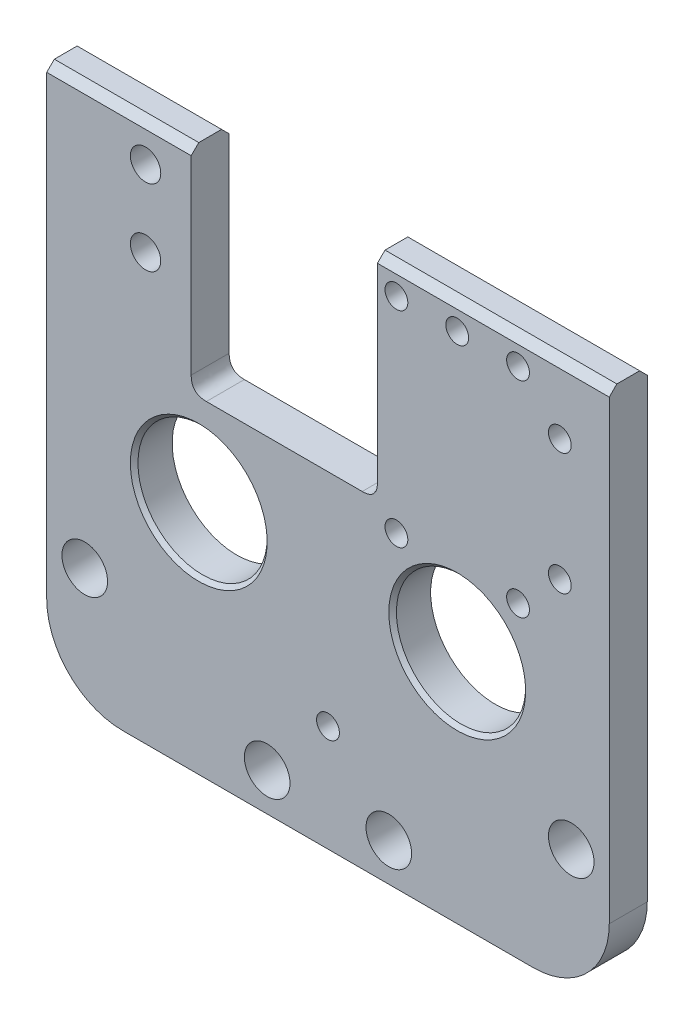
SolidWorks part; units mm, degrees
material "Stop 1060"
ref_plane "Płaszczyzna przednia" through (0, 0, 0) normal (0, 0, 1) x (1, 0, 0)
ref_plane "Płaszczyzna górna" through (0, 0, 0) normal (0, 1, 0) x (1, 0, 0)
ref_plane "Płaszczyzna prawa" through (0, 0, 0) normal (1, 0, 0) x (0, 0, -1)
sketch "Szkic1" plane through (0, 0, 0) normal (0, 0, 1) x (1, 0, 0)
  line L2 (34, 36) -> (34, -35)
  line L3 (34, -35) -> (-20, -35)
  line L6 (-20, -35) -> (-20, 36)
  line L7 (-20, 36) -> (34, 36)
  dimension "D1" = 71
  dimension "D2" = 20
  dimension "D3" = 54
  dimension "D4" = 36
extrude "Dodanie-wyciągnięcie1" add sketch "Szkic1" along normal blind 5
sketch "Szkic2" plane through (0, 0, 5) normal (0, 0, 1) x (1, 0, 0)
  line L1 (-20, 36) -> (3.5, 36)
  line L2 (-20, 36) -> (-20, 8)
  line L3 (-20, 8) -> (3.5, 8)
  line L4 (3.5, 36) -> (3.5, 8)
  dimension "D1" = 28
  dimension "D2" = 23.5
extrude "Wytnij-wyciągnięcie1" cut sketch "Szkic2" against normal blind 5
sketch "Szkic3" plane through (0, 0, 0) normal (0, 0, -1) x (-1, 0, 0)
  line L0 (-3.5, 8) -> (-3.5, 36) construction
  line L1 (-3.5, 30.5) -> (-24.5, 30.5)
  line L2 (-3.5, 30.5) -> (-3.5, 9.5)
  line L3 (-3.5, 9.5) -> (-24.5, 9.5)
  line L4 (-24.5, 30.5) -> (-24.5, 9.5)
  line L5 (-34, 36) -> (-3.5, 36) construction
  dimension "D1" = 5.5
  dimension "D2" = 21
  dimension "D3" = 21
extrude "Wytnij-wyciągnięcie2" cut sketch "Szkic3" against normal blind 3
sketch "Szkic4" plane through (0, 0, 5) normal (0, 0, 1) x (1, 0, 0)
  line L0 (3.5, 8) -> (3.5, 36) construction
  line L1 (34, 36) -> (3.5, 36) construction
  circle A0 centre (6, 32.5) radius 1.5
  circle A1 centre (14, 32.5) radius 1.5
  circle A2 centre (22, 32.5) radius 1.5
  circle A4 centre (22, 5.5) radius 1.5
  circle A5 centre (6, 5.5) radius 1.5
  circle A6 centre (27.5, 27) radius 1.5
  circle A7 centre (27.5, 11) radius 1.5
  circle A8 centre (14, 5.5) radius 1.5 [skipped]
  dimension "D1" = 2.5
  dimension "D2" = 3
  dimension "D4" = 3
  dimension "D6" = 8
  dimension "D8" = 5.5
  dimension "D10" = 3
  dimension "D3" = 3.5
  dimension "D5" = 2
  dimension "D7" = 27
  dimension "D9" = 5.5
  dimension "D11" = 2
extrude "Wytnij-wyciągnięcie3" cut sketch "Szkic4" against normal blind 5
sketch "Szkic5" plane through (0, 0, 5) normal (0, 0, 1) x (1, 0, 0)
  line L1 (-20, 8) -> (-40, 8)
  line L2 (-20, 8) -> (-20, -35)
  line L3 (-20, -35) -> (-40, -35)
  line L4 (-40, 8) -> (-40, -35)
  dimension "D1" = 20
  dimension "D2" = 43
extrude "Dodanie-wyciągnięcie2" add sketch "Szkic5" against normal blind 5
sketch "Szkic6" plane through (0, 0, 5) normal (0, 0, 1) x (1, 0, 0)
  line L0 (-40, 8) -> (-40, -35) construction
  line L1 (-40, 8) -> (3.5, 8) construction
  circle A0 centre (-20, -4) radius 8.5
  circle A1 centre (14, -4) radius 8.5
  dimension "D1" = 20
  dimension "D3" = 17
  dimension "D2" = 12
  dimension "D5" = 34
  dimension "D4" = 2
extrude "Wytnij-wyciągnięcie4" cut sketch "Szkic6" against normal blind 5
sketch "symetria" plane through (0, 0, 5) normal (0, 0, 1) x (1, 0, 0)
  line L0 (-20, -4) -> (14, -4)
  line L1 (-3, -4) -> (-3, -39)
  dimension "D1" = 35
sketch "Szkic7" plane through (0, 0, 5) normal (0, 0, 1) x (1, 0, 0)
  line L0 (-3, -4) -> (-3, -39) construction
  line L1 (-40, -35) -> (34, -35) construction
  line L2 (-3, -36.4153) -> (-3, -30)
  line L3 (-40, 8) -> (-40, -35) construction
  circle A0 centre (5, -30) radius 3
  circle A1 centre (-11, -30) radius 3
  circle A2 centre (-35, -19) radius 3
  circle A3 centre (29, -19) radius 3
  dimension "D1" = 6
  dimension "D4" = 6
  dimension "D2" = 8
  dimension "D3" = 5
  dimension "D5" = 5
  dimension "D6" = 16
extrude "Wytnij-wyciągnięcie5" cut sketch "Szkic7" against normal blind 10 contours A1 | A0 | A2 | A3 region at (5, -30, 5) region at (-11, -30, 5) region at (-35, -19, 5) region at (29, -19, 5)
fillet "Zaokrąglenie3" radius 10 2 edges at (34, -35, 2.5) (-40, -35, 2.5)
sketch "Szkic8" plane through (0, 0, 5) normal (0, 0, 1) x (1, 0, 0)
  line L1 (-40, 8) -> (-21, 8)
  line L2 (-40, 8) -> (-40, 36)
  line L3 (-40, 36) -> (-21, 36)
  line L4 (-21, 8) -> (-21, 36)
  dimension "D1" = 19
  dimension "D2" = 28
extrude "Dodanie-wyciągnięcie3" add sketch "Szkic8" against normal blind 5
fillet "Zaokrąglenie2" radius 2 2 edges at (3.5, 8, 2.5) (-21, 8, 2.5) conic rho 0.5
sketch "Szkic9" plane through (0, 0, 5) normal (0, 0, 1) x (1, 0, 0)
  line L2 (-21, 10) -> (-21, 36) construction
  line L3 (-21, 36) -> (-40, 36) construction
  circle A1 centre (-27, 31) radius 2
  circle A2 centre (-27, 21) radius 2
  dimension "D1" = 6
  dimension "D2" = 6
  dimension "D3" = 4
  dimension "D4" = 4
  dimension "D6" = 10
  dimension "D5" = 5
extrude "Wytnij-wyciągnięcie6" cut sketch "Szkic9" against normal blind 10
chamfer "Sfazowanie2" distance 1 angle 45 4 edges at (18.75, 36, 5) (18.75, 36, 0) (-30.5, 36, 0) (-30.5, 36, 5)
chamfer "Sfazowanie3" distance 0.5 angle 45 2 edges at (-11.5, -4, 5) (22.5, -4, 5)
sketch "Szkic10" plane through (0, 0, 5) normal (0, 0, 1) x (1, 0, 0)
  line L0 (-3, -4) -> (-3, -39) construction
  line L1 (-30, -35) -> (24, -35) construction
  circle A0 centre (-3, -21) radius 1.5
  dimension "D1" = 14
  dimension "D2" = 3
extrude "Wytnij-wyciągnięcie7" cut sketch "Szkic10" against normal blind 10
